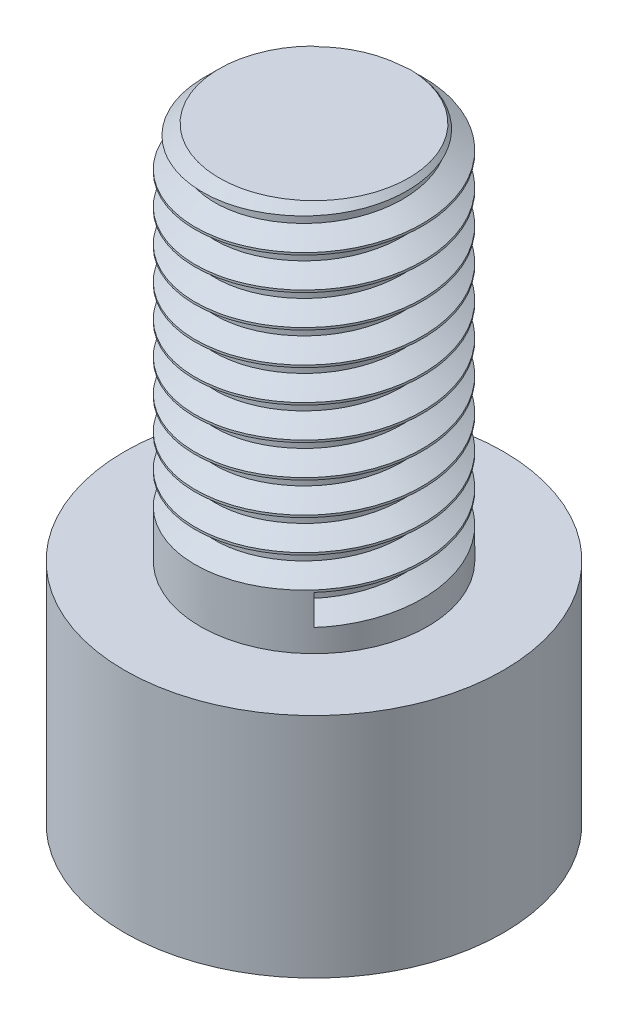
SolidWorks part; units mm, degrees
ref_plane "Ön Düzlem" through (0, 0, 0) normal (0, 0, 1) x (1, 0, 0)
ref_plane "Üst Düzlem" through (0, 0, 0) normal (0, 1, 0) x (1, 0, 0)
ref_plane "Sağ Düzlem" through (0, 0, 0) normal (1, 0, 0) x (0, 0, -1)
sketch "Çizim1" plane through (0, 0, 0) normal (0, 1, 0) x (1, 0, 0)
  circle A0 centre (0, 0) radius 2.5
  dimension "D1" = 5
extrude "Yükseklik-Ekstrüzyon2" add sketch "Çizim1" along normal blind 3
sketch "Çizim3" plane through (0, 3, 0) normal (0, 1, 0) x (1, 0, 0)
  circle A0 centre (0, 0) radius 1.5
  dimension "D1" = 3
extrude "Yükseklik-Ekstrüzyon3" add sketch "Çizim3" along normal blind 5
chamfer "Pah1" distance 0.25 angle 45 1 edges at (0, 8, 1.5)
sketch "Çizim4" plane through (0, 8, 0) normal (0, 1, 0) x (1, 0, 0)
  circle A0 centre (0, 0) radius 1.5
  dimension "D1" = 3
curve "Helis/Spiral1" pitch 0.4286 height 4.5 turns 10.5
ref_plane "Düzlem2" through (-1.0607, 8, -1.0607) normal (-0.7071, 0, 0.7071) x (0.7071, 0, 0.7071)
sketch "Çizim6" plane through (-1.0607, 8, -1.0607) normal (-0.7071, 0, 0.7071) x (0.7071, 0, 0.7071)
  line L0 (0, 0) -> (0.2262, 0) construction
  line L1 (0, 0.2) -> (0, -0.2)
  line L2 (0, -0.2) -> (0.2598, -0.05)
  line L3 (0.2598, -0.05) -> (0.2598, 0.05)
  line L4 (0.2598, 0.05) -> (0, 0.2)
  point P2 (0, 0)
  point P7 (0.2598, 0)
  dimension "D1" = 0.4
  dimension "D2" = 60
  dimension "D3" = 0.1
sweep "Kes-Süpür3" cut profiles "Çizim6" path "Helis/Spiral1"
